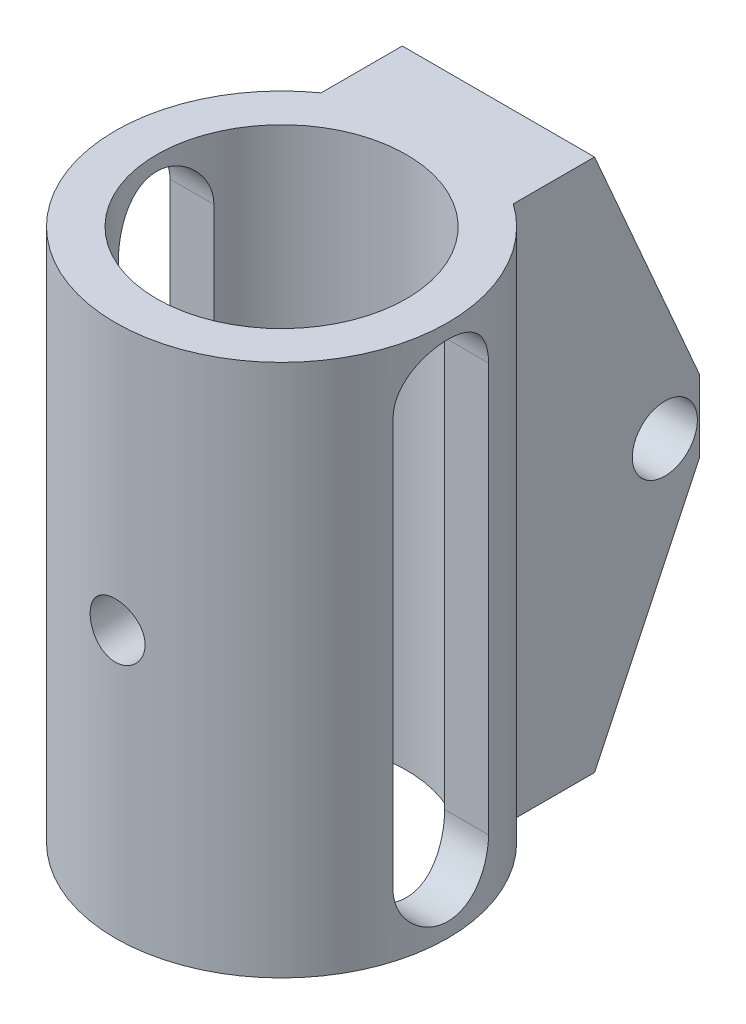
SolidWorks part; units mm, degrees
ref_plane "Front Plane" through (0, 0, 0) normal (0, 0, 1) x (1, 0, 0)
ref_plane "Top Plane" through (0, 0, 0) normal (0, 1, 0) x (1, 0, 0)
ref_plane "Right Plane" through (0, 0, 0) normal (1, 0, 0) x (0, 0, -1)
sketch "Sketch1" plane through (0, 0, 0) normal (0, 1, 0) x (1, 0, 0)
  circle A0 centre (0, 0) radius 8.6383
  circle A1 centre (0, 0) radius 11.5
  dimension "D1" = 17.2766
  dimension "D2" = 23
extrude "Boss-Extrude1" add sketch "Sketch1" along normal blind 36.88
ref_plane "Plane1" through (-11.5, 0, 0) normal (-1, 0, 0) x (0, 0, 1)
sketch "Sketch2" plane through (-11.5, 0, 0) normal (-1, 0, 0) x (0, 0, 1)
  line L0 (0, 32.5733) -> (0, 4.3067) construction
  line L1 (3.302, 32.5733) -> (3.302, 4.3067)
  line L2 (-3.302, 32.5733) -> (-3.302, 4.3067)
  line L3 (0, 32.5733) -> (0, 36.88) construction
  line L4 (8.6383, 36.88) -> (-8.6383, 36.88) construction
  line L5 (0, 4.3067) -> (0, 0) construction
  arc A0 (3.302, 32.5733) -> (-3.302, 32.5733) centre (0, 32.5733) ccw
  arc A1 (-3.302, 4.3067) -> (3.302, 4.3067) centre (0, 4.3067) ccw
  point P3 (0, 18.44)
  dimension "D1" = 3.302
extrude "Cut-Extrude1" cut sketch "Sketch2" against normal blind 55.88
sketch "Sketch3" plane through (0, 0, 0) normal (0, 0, 1) x (1, 0, 0)
  line L0 (0, 36.88) -> (0, 18.44) construction
  line L1 (11.5, 36.88) -> (-11.5, 36.88) construction
  circle A0 centre (0, 18.44) radius 1.9
  dimension "D1" = 3.8
  dimension "D2" = 18.44
extrude "Cut-Extrude2" cut sketch "Sketch3" along normal through all
sketch "Sketch4" plane through (0, 0, 0) normal (0, 0, 1) x (1, 0, 0)
  line L0 (-8.6383, 0) -> (-6.6495, 0) construction
  line L5 (8.6383, 0) -> (6.6495, 0) construction
  line L6 (8.6383, 36.88) -> (6.6495, 36.88) construction
  line L7 (-8.6383, 36.88) -> (-6.6495, 36.88) construction
  line L9 (6.6495, 0) -> (-6.6495, 0)
  line L10 (6.6495, 0) -> (6.6495, 36.88)
  line L11 (6.6495, 36.88) -> (-6.6495, 36.88)
  line L12 (-6.6495, 0) -> (-6.6495, 36.88)
  dimension "D1" = 6.6495
  dimension "D2" = 8.6383
  dimension "D3" = 6.6495
  dimension "D4" = 36.88
extrude "Boss-Extrude2" add sketch "Sketch4" along normal up to surface (5.6174 mm away) from offset 15 up to face at (11.2557, 18.44, 0) offset against normal yes
sketch "Sketch5" plane through (-6.6495, 0, 0) normal (-1, 0, 0) x (0, 0, 1)
  line L0 (-22.264, 15.2344) -> (-22.264, 20.2202)
  line L1 (-15, 36.88) -> (-22.264, 20.2202)
  line L2 (-22.264, 15.2344) -> (-15, 0)
  line L3 (-15, 17.577) -> (-19.8654, 17.577) construction
  line L4 (-15, 36.88) -> (-15, 0) construction
  circle A0 centre (-19.8654, 17.577) radius 2.25
  point P6 (-22.2657, 17.577)
  line M4 (-15, 36.88) -> (-15, 0)
  dimension "D1" = 4.5
extrude "Boss-Extrude3" add sketch "Sketch5" along direction (-1, 0, 0) on the side against the normal up to surface (13.299 mm away) contours L0 L2 L1 A0 M4 region at (-6.6495, 18.2439, -17.4579) up to face at (6.6495, 18.44, -12.1913)
